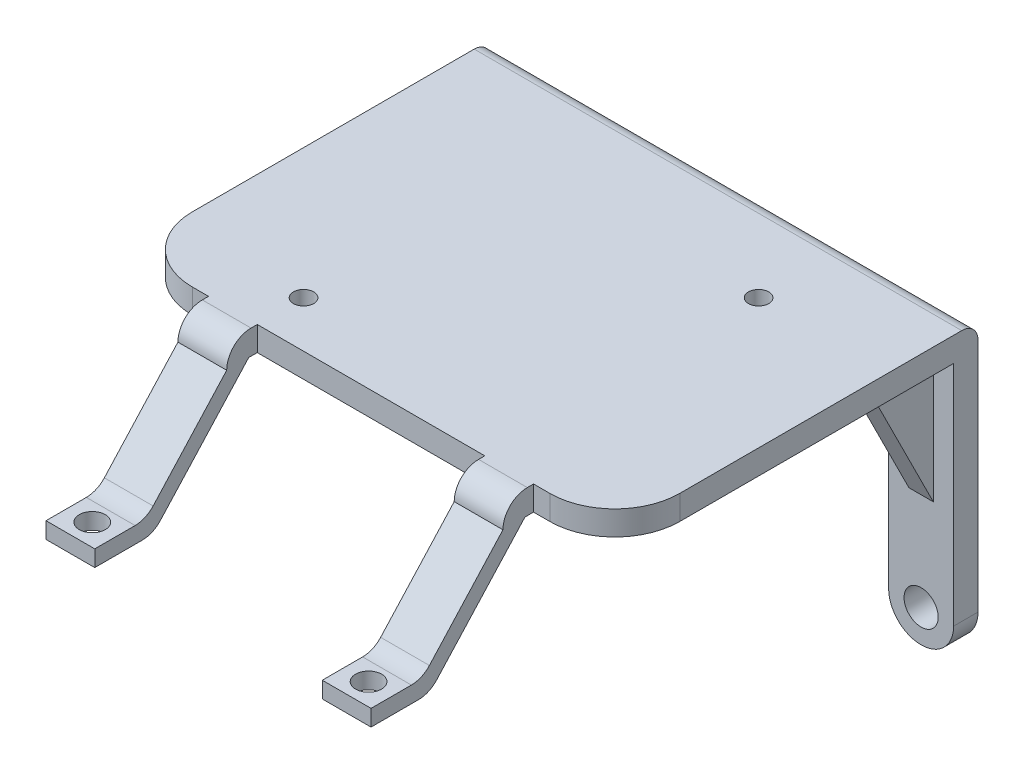
SolidWorks part; units mm, degrees
ref_plane "前视基准面" through (0, 0, 0) normal (0, 0, 1) x (1, 0, 0)
ref_plane "上视基准面" through (0, 0, 0) normal (0, 1, 0) x (1, 0, 0)
ref_plane "右视基准面" through (0, 0, 0) normal (1, 0, 0) x (0, 0, -1)
other "Configuration Table"
sketch "草图1" plane through (0, 0, 0) normal (0, 1, 0) x (1, 0, 0)
  line L1 (30, -25) -> (-30, -25)
  line L2 (30, -25) -> (30, 25)
  line L3 (30, 25) -> (-30, 25)
  line L4 (-30, -25) -> (-30, 25)
  line L5 (30, -25) -> (-30, 25) construction
  line L6 (30, 25) -> (-30, -25) construction
  point P0 (0, 0)
  dimension "D1" = 60
  dimension "D2" = 50
extrude "凸台-拉伸1" add sketch "草图1" along normal blind 3
sketch "草图2" plane through (0, 3, 0) normal (0, 1, 0) x (1, 0, 0)
  line L0 (0, 0) -> (0, 19.8) construction
  line L7 (14.0007, 14.0007) -> (-14.0007, -14.0007) construction
  circle A4 centre (0, 0) radius 19.8 construction
  circle A5 centre (-14.0007, -14.0007) radius 1.25
  circle A6 centre (14.0007, 14.0007) radius 1.25
  point P0 (0, 0)
  point P16 (0, 0)
  dimension "D7" = 39.6
  dimension "D8" = 135
  dimension "D9" = 2.5
  dimension "D10" = 2.5
extrude "切除-拉伸1" cut sketch "草图2" against normal blind 3
sketch "草图4" plane through (30, 0, 0) normal (1, 0, 0) x (0, 0, -1)
  line L2 (25, 0) -> (22, 0)
  line L3 (25, 0) -> (25, -28)
  line L6 (25, -28) -> (22, -28)
  line L7 (22, 0) -> (22, -28)
  dimension "D1" = 3
  dimension "D2" = 28
extrude "凸台-拉伸3" add sketch "草图4" against normal up to surface (60 mm away) up to face at (-30, 1.5, 0)
sketch "草图5" plane through (0, 0, -25) normal (0, 0, -1) x (-1, 0, 0)
  line L0 (30, -28) -> (-30, -28) construction
  line L1 (-22, -28) -> (22, -28)
  line L2 (-22, -28) -> (-22, 0)
  line L3 (-22, 0) -> (22, 0)
  line L4 (22, -28) -> (22, 0)
  line L5 (-30, 3) -> (-30, -28) construction
  line L6 (30, 3) -> (30, -28) construction
  line L7 (-30, 3) -> (30, 3) construction
  dimension "D1" = 8
  dimension "D2" = 8
  dimension "D3" = 3
extrude "切除-拉伸2" cut sketch "草图5" against normal blind 10
sketch "草图7" plane through (0, 0, -22) normal (0, 0, 1) x (1, 0, 0)
  line L0 (22, -28) -> (30, -28) construction
  line L1 (-30, -28) -> (-22, -28) construction
  line L2 (-30, -28) -> (-22, -28)
  line L3 (22, -28) -> (30, -28)
  arc A0 (22, -28) -> (30, -28) centre (26, -28) ccw
  arc A1 (-30, -28) -> (-22, -28) centre (-26, -28) ccw
extrude "凸台-拉伸4" add sketch "草图7" against normal up to surface (3 mm away) up to face at (0, -13.25, -25)
sketch "草图8" plane through (0, 0, -22) normal (0, 0, 1) x (1, 0, 0)
  circle A0 centre (26, -28) radius 2.1
  circle A1 centre (-26, -28) radius 2.1
  dimension "D1" = 4.2
  dimension "D2" = 4.2
extrude "切除-拉伸3" cut sketch "草图8" against normal through all
sketch "草图3" plane through (30, 0, 0) normal (1, 0, 0) x (0, 0, -1)
  line L6 (-20.7564, 0) -> (-32.5241, -12.9138)
  line L7 (-25, 0) -> (22, 0) construction
  line L9 (-32.5241, -12.9138) -> (-39.6978, -12.9138)
  line L10 (-36.9364, -12.9138) -> (-111.9365, -12.9138) construction
  line L11 (-39.6978, -12.9138) -> (-39.6978, -10.9138)
  line L12 (-39.6978, -10.9138) -> (-33.4074, -10.9138)
  line L13 (-33.4074, -10.9138) -> (-23.4623, 0)
  line L14 (-31.949, -12.9138) -> (-36.9364, -12.9138) construction
  line L15 (-23.4623, 0) -> (-20.7564, 0)
  dimension "D1" = 2
  dimension "D2" = 2
extrude "凸台-拉伸5" add sketch "草图3" against normal up to surface (60 mm away) up to face at (-30, -8.3333, -7.3333)
sketch "草图9" plane through (0, -12.9138, 0) normal (0, -1, 0) x (1, 0, 0)
  line L0 (-30, 39.6978) -> (30, 39.6978) construction
  line L1 (20, 39.6978) -> (30, 39.6978)
  line L2 (20, 39.6978) -> (20, 19.6978)
  line L3 (20, 19.6978) -> (30, 19.6978)
  line L4 (30, 39.6978) -> (30, 19.6978)
  line L5 (30, 20.7564) -> (30, -22) construction
  line L7 (-14, 39.6978) -> (14, 39.6978)
  line L8 (-14, 39.6978) -> (-14, 19.6978)
  line L9 (-14, 19.6978) -> (14, 19.6978)
  line L10 (14, 39.6978) -> (14, 19.6978)
  line L11 (-30, -22) -> (-30, 20.7564) construction
  line L12 (-20, 39.6978) -> (-30, 39.6978)
  line L13 (-20, 39.6978) -> (-20, 19.6978)
  line L14 (-20, 19.6978) -> (-30, 19.6978)
  line L15 (-30, 39.6978) -> (-30, 19.6978)
  dimension "D1" = 10
  dimension "D2" = 10
  dimension "D3" = 28
  dimension "D4" = 6
  dimension "D5" = 20
extrude "切除-拉伸4" cut sketch "草图9" against normal through all
sketch "草图11" plane through (0, -12.9138, 0) normal (0, -1, 0) x (1, 0, 0)
  circle A0 centre (17, 37) radius 1.6
  circle A1 centre (-17, 37) radius 1.6
  dimension "D1" = 3.2
  dimension "D2" = 3.2
extrude "切除-拉伸5" cut sketch "草图11" against normal through all
sketch "草图12" plane through (20, 0, 0) normal (1, 0, 0) x (0, 0, -1)
  line L1 (-23.4623, 0) -> (-25, 0)
  line L2 (-23.4623, 0) -> (-23.4623, 3)
  line L3 (-23.4623, 3) -> (-25, 3)
  line L4 (-25, 0) -> (-25, 3)
extrude "切除-拉伸6" cut sketch "草图12" against normal through all
fillet "圆角1" radius 8 1 edges at (30, 1.5, 19.6978)
fillet "圆角2" radius 8 1 edges at (-30, 1.5, 19.6978)
fillet "圆角3" radius 3 2 edges at (17, 3, 23.4623) (-17, 3, 23.4623)
fillet "圆角4" radius 3 4 edges at (17, -10.9138, 33.4074) (17, -12.9138, 32.5241) (-17, -12.9138, 32.5241) (-17, -10.9138, 33.4074)
fillet "圆角5" radius 2 1 edges at (0, 3, -25)
ref_plane "基准面1" through (26, 0, 0) normal (1, 0, 0) x (0, 0, -1)
sketch "草图14" plane through (26, 0, 0) normal (1, 0, 0) x (0, 0, -1)
  line L0 (14, 0) -> (22, -16)
  line L1 (-11.6978, 0) -> (22, 0) construction
  line L2 (22, 0) -> (22, -28) construction
  dimension "D1" = 8
  dimension "D2" = 16
rib "筋2" sketch "草图14" sketch "草图14" thickness 3 extrusion direction parallel to sketch draft on no parameters "D1"=3
ref_plane "基准面2" through (-26, 0, 0) normal (-1, 0, 0) x (0, 0, 1)
sketch "草图16" plane through (-26, 0, 0) normal (-1, 0, 0) x (0, 0, 1)
  line L0 (-14, 0) -> (-22, -16)
  line L1 (-22, 0) -> (11.6978, 0) construction
  line L2 (-22, -28) -> (-22, 0) construction
  dimension "D1" = 8
  dimension "D2" = 16
rib "筋3" sketch "草图16" sketch "草图16" thickness 3 extrusion direction parallel to sketch draft on no parameters "D1"=3
ref_plane "基准面3" through (17, 0, 0) normal (1, 0, 0) x (0, 0, -1)
sketch "草图17" plane through (17, 0, 0) normal (1, 0, 0) x (0, 0, -1)
  line L0 (-25.1183, -4.7867) -> (-18.4538, 0)
  line L1 (-31.6316, -11.9345) -> (-20.7564, 0) construction
  line L2 (-19.6978, 0) -> (-11.6978, 0) construction
rib "筋4" sketch "草图17" sketch "草图17" thickness 2 extrusion direction parallel to sketch draft on no parameters "D1"=2
ref_plane "基准面4" through (-17, 0, 0) normal (-1, 0, 0) x (0, 0, 1)
sketch "草图18" plane through (-17, 0, 0) normal (-1, 0, 0) x (0, 0, 1)
  line L0 (18.4538, 0) -> (25.0579, -4.7204)
  line L1 (20.7564, 0) -> (31.6316, -11.9345) construction
rib "筋5" sketch "草图18" sketch "草图18" thickness 2 extrusion direction parallel to sketch draft on no parameters "D1"=2
